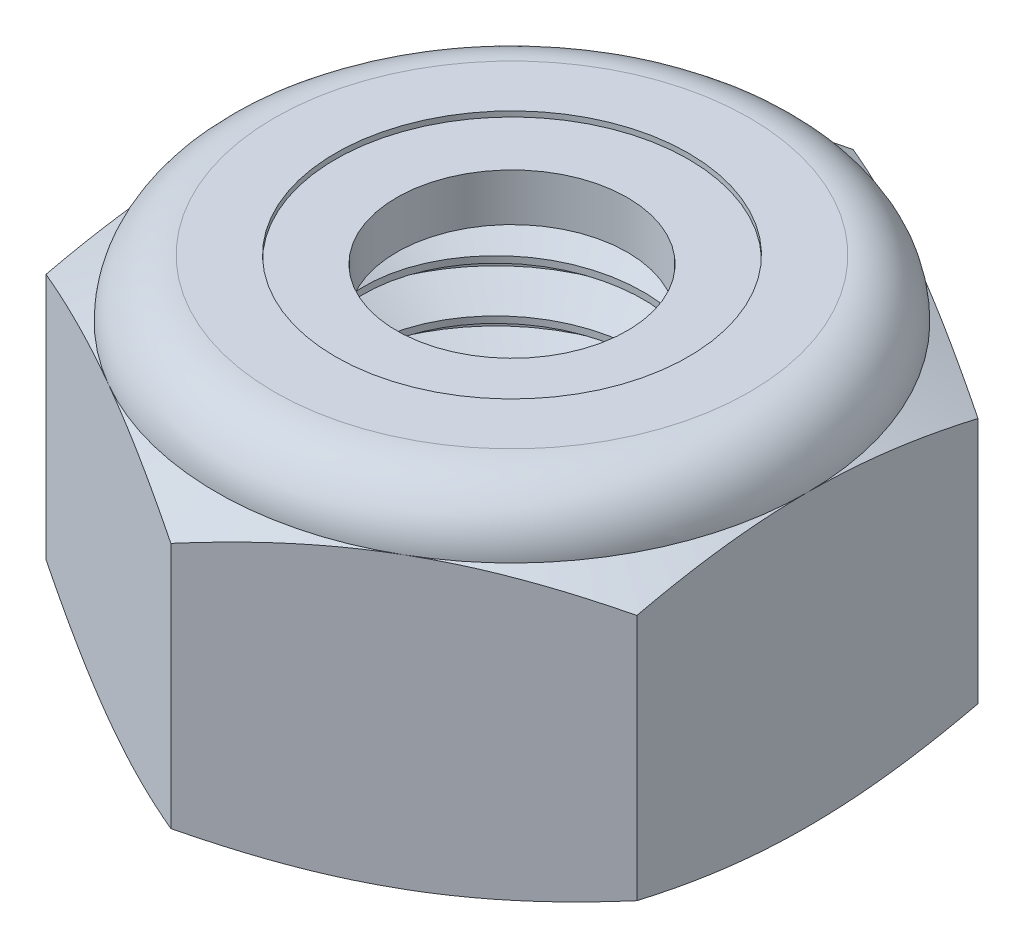
SolidWorks part; units mm, degrees
ref_plane "Front" through (0, 0, 0) normal (0, 0, 1) x (1, 0, 0)
ref_plane "Top" through (0, 0, 0) normal (0, 1, 0) x (1, 0, 0)
ref_plane "Right" through (0, 0, 0) normal (1, 0, 0) x (0, 0, -1)
sketch "Sketch1" plane through (0, 0, 0) normal (0, 1, 0) x (1, 0, 0)
  line L0 (0, 0) -> (3.5355, -3.5355) construction
  line L1 (0, 9.815) -> (-8.5, 4.9075)
  line L2 (-8.5, 4.9075) -> (-8.5, -4.9075)
  line L3 (-8.5, -4.9075) -> (0, -9.815)
  line L4 (0, -9.815) -> (8.5, -4.9075)
  line L5 (8.5, -4.9075) -> (8.5, 4.9075)
  line L6 (8.5, 4.9075) -> (0, 9.815)
  circle A0 centre (0, 0) radius 8.5 construction
  circle A1 centre (0, 0) radius 5
  point P12 (3.5355, -3.5355)
  dimension "Thread Dia" = 10
  dimension "Hex Flats" = 17
  dimension "D1" = 45
extrude "Extrude1" add sketch "Sketch1" along normal blind 10
chamfer "Chamfer1" distance 0.5 angle 45 1 edges at (0, 0, 5)
sketch "Sketch5" plane through (0, 0, 0) normal (1, 0, 0) x (0, 0, -1)
  line L0 (0, 0) -> (8.5, 0)
  line L1 (8.5, 0) -> (9.815, 0.6132)
  line L2 (9.815, 0.6132) -> (9.815, 7.7202)
  line L3 (9.815, 7.7202) -> (8.5, 8.3333)
  line L4 (6.8333, 10) -> (6.8333, 11.27)
  line L5 (6.8333, 11.27) -> (11.085, 11.27)
  line L6 (11.085, 11.27) -> (11.085, -1.27)
  line L7 (11.085, -1.27) -> (0, -1.27)
  line L8 (0, -1.27) -> (0, 0)
  line L9 (8.5, 8.3333) -> (8.5, 0) construction
  line L10 (4.9075, 10) -> (9.815, 10) construction
  line L13 (9.815, 4.1667) -> (11.085, 4.1667) construction
  line L14 (9.815, 10) -> (9.815, 0) construction
  line L15 (0, 0) -> (0, 11.27) construction
  line L20 (0, 11.27) -> (6.8333, 11.27) construction
  arc A0 (8.5, 8.3333) -> (6.8333, 10) centre (6.8333, 8.3333) ccw
  dimension "D1" = 25
  dimension "D2" = 1.27
  dimension "D3" = 10
  dimension "D4" = 1.6667
revolve "Cut-Revolve3" cut sketch "Sketch5" angle 360 about L15
sketch "Sketch6" plane through (0, 0, 0) normal (1, 0, 0) x (0, 0, -1)
  line L0 (0, 8.3333) -> (8.3476, 8.3333)
  line L1 (6.8333, 9.8476) -> (5.0762, 9.8476)
  line L2 (0, 11.27) -> (0, 8.3333)
  line L3 (5.0762, 11.27) -> (0, 11.27)
  line L4 (0, 11.27) -> (6.8333, 11.27) construction
  line L5 (0, 0) -> (0, 11.27) construction
  line L6 (0, 11.27) -> (0, 0) construction
  line L7 (5.0762, 9.8476) -> (5.0762, 11.27)
  line L8 (6.8333, 10) -> (6.8333, 9.8476) construction
  line L9 (5.0762, 9.8476) -> (4.9238, 9.8476) construction
  line L21 (5, 9.8476) -> (5, 10) construction
  arc A0 (8.3476, 8.3333) -> (6.8333, 9.8476) centre (6.8333, 8.3333) ccw
  arc A1 (8.5, 8.3333) -> (6.8333, 10) centre (6.8333, 8.3333) ccw construction
  dimension "D1" = 0.1524
revolve "Cut-Revolve4" cut sketch "Sketch6" angle 360 about L6
sketch "Sketch7" plane through (0, 0, 0) normal (1, 0, 0) x (0, 0, -1)
  line L0 (3.3191, 8.4095) -> (8.2694, 8.4095)
  line L1 (6.8333, 9.7714) -> (3.3191, 9.7714)
  line L2 (3.3191, 9.7714) -> (3.3191, 8.4095)
  line L3 (3.3191, 8.4095) -> (0, 8.4095) construction
  line L4 (0, 8.4095) -> (0, 9.7714) construction
  line L5 (0, 9.7714) -> (3.3191, 9.7714) construction
  line L6 (3.3191, 8.4095) -> (3.3191, 8.3333) construction
  line L7 (0, 8.3333) -> (8.3476, 8.3333) construction
  line L8 (6.8333, 9.7714) -> (6.8333, 9.8476) construction
  line L10 (3.3191, 9.8476) -> (5.0762, 9.8476) construction
  line L11 (6.8333, 9.8476) -> (5.0762, 9.8476) construction
  arc A0 (8.2694, 8.4095) -> (6.8333, 9.7714) centre (6.8333, 8.3333) ccw
  arc A2 (8.3476, 8.3333) -> (6.8333, 9.8476) centre (6.8333, 8.3333) ccw construction
  dimension "D1" = 0.0762
revolve "Revolve2" add sketch "Sketch7" angle 360 about L4
ref_axis "Center Axis 1" through (0, 8.3333, 0) along (0, -1, 0)
sketch "Sketch12" plane through (0, 0, 0) normal (0, -1, 0) x (1, 0, 0)
  circle A0 centre (0, 0) radius 5
  circle A1 centre (0, 0) radius 5 construction
extrude "Boss-Extrude3" add sketch "Sketch12" against normal up to vertex (8.3333 mm away) up to point (0, 8.3333, -8.3476)
sketch "Sketch2" plane through (0, 0, 0) normal (1, 0, 0) x (0, 0, -1)
  line L1 (0, 0) -> (5, 0)
  line L2 (0, 0) -> (0, 9.8476)
  line L3 (0, 9.8476) -> (5, 9.8476)
  line L4 (5, 0) -> (5, 9.8476)
  line L7 (0, -5) -> (0, 0) construction
  line L11 (6.8333, 9.8476) -> (5.0762, 9.8476) construction
revolve "Revolve1" add sketch "Sketch2" angle 360 about L7
sketch "Sketch8" plane through (0, 0, 0) normal (0, -1, 0) x (1, 0, 0)
  circle A0 centre (0, 0) radius 5 construction
  circle A2 centre (0, 0) radius 5
curve "Helix/Spiral1" pitch 1.5 height 20 radius 5 centre (0, 0, 0) axis (0, 1, 0) start towards (0, 0, -1) parameters "Pitch"=1.5
sketch "Sketch9" plane through (0, 0, 0) normal (1, 0, 0) x (0, 0, -1)
  line L0 (5, -1.3125) -> (5, 0)
  line L1 (5, -1.3125) -> (4.0257, -0.75)
  line L2 (4.0257, -0.75) -> (4.0257, -0.5625)
  line L3 (4.0257, -0.5625) -> (5, 0)
  line L4 (-5, 0) -> (5, 0) construction
  line L5 (5, -0.6562) -> (4.0257, -0.6562) construction
  line L6 (4.5129, -1.0312) -> (4.5129, -0.2813) construction
  dimension "D1" = 0.1875
  dimension "D2" = 0.75
  dimension "D3" = 60
sweep "Cut-Sweep1" cut profiles "Sketch9" path "Helix/Spiral1" align with end faces yes
combine bodies "Combine1" operation type subtract main body 135 bodies to subtract 132
sketch "Sketch14" plane through (0, 0, 0) normal (1, 0, 0) x (0, 0, -1)
  line L0 (0, 0) -> (0, 10) construction
  line L1 (5.0762, 10) -> (-5.0762, 10) construction
  line L2 (-5.5, 0) -> (-2.5, 3)
  line L4 (-5, 0) -> (-5.5, 0)
  line L9 (-2.5, 3) -> (0, 3)
  line L10 (0, 3) -> (0, 0)
  line L11 (0, 0) -> (-5, 0)
  line L12 (-2.5, 3) -> (-2.5, 0) construction
  dimension "D1" = 45
  dimension "D2" = 10
  dimension "D3" = 0.5
revolve "Cut-Revolve5" cut sketch "Sketch14" angle 360 about L0
equation "\"D4@Sketch5\"=\"Height@Extrude1\"/6"
equation "\"D3@Helix/Spiral1\"=2*\"Height@Extrude1\""
equation "\"D1@Sketch9\"=\"Pitch@Helix/Spiral1\"*.125"
equation "\"D2@Sketch9\"=\"Pitch@Helix/Spiral1\"*.50"
equation "\"D1@Chamfer1\"=.05*\"Thread Dia@Sketch1\""
equation "\"D2@Sketch14\"=\"Thread Dia@Sketch1\""
equation "\"D3@Sketch14\"=\"D1@Chamfer1\""
